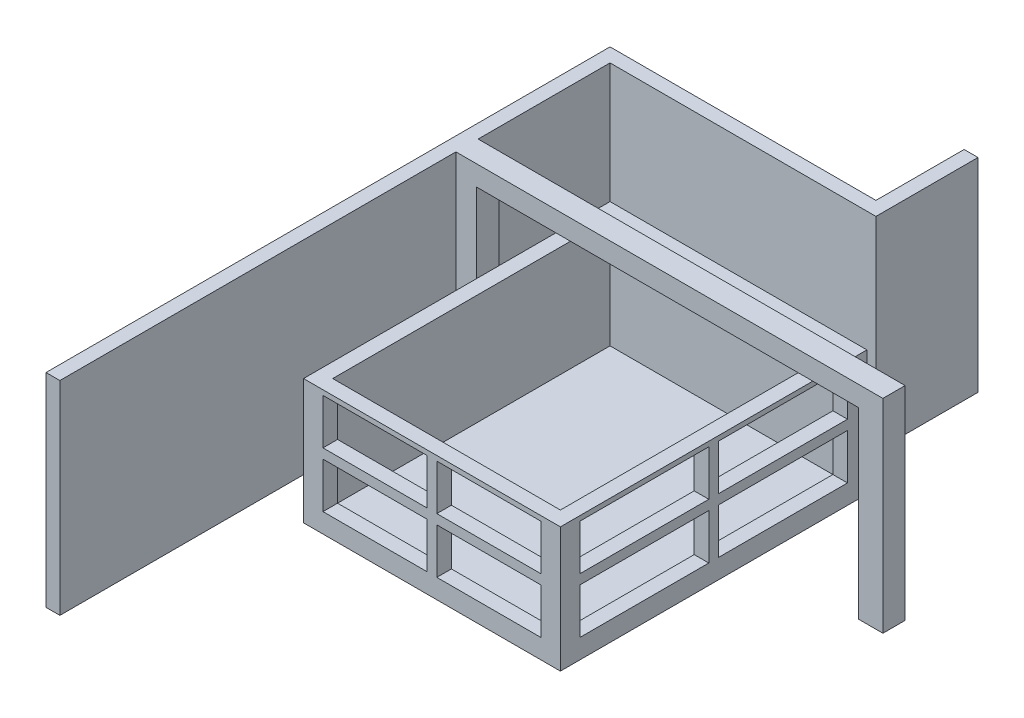
SolidWorks part; units mm, degrees
ref_plane "Front Plane" through (0, 0, 0) normal (0, 0, 1) x (1, 0, 0)
ref_plane "Top Plane" through (0, 0, 0) normal (0, 1, 0) x (1, 0, 0)
ref_plane "Right Plane" through (0, 0, 0) normal (1, 0, 0) x (0, 0, -1)
sketch "Sketch1" plane through (0, 0, 0) normal (0, 1, 0) x (1, 0, 0)
  line L0 (-1640, -1997.5) -> (-1640, 1997.5)
  line L1 (-1850, -2207.5) -> (1850, -2207.5)
  line L2 (-1850, -2207.5) -> (-1850, 2207.5)
  line L3 (-1850, 2207.5) -> (1850, 2207.5)
  line L4 (1850, -2207.5) -> (1850, 2207.5)
  line L5 (-1850, -2207.5) -> (1850, 2207.5) construction
  line L6 (-1850, 2207.5) -> (1850, -2207.5) construction
  line L7 (-1640, 1997.5) -> (1640, 1997.5)
  line L8 (1640, -1997.5) -> (1640, 1997.5)
  line L9 (-1640, -1997.5) -> (1640, -1997.5)
  point P0 (0, 0)
  dimension "D1" = 3700
  dimension "D2" = 4415
  dimension "D3" = 210
extrude "Boss-Extrude1" add sketch "Sketch1" along normal blind 210 contours L0 L9 L8 L7 | L1 L4 L3 L2 L9 L0 L7 L8 region at (0, 0, 0) region at (-1792.396, 0, 0)
extrude "Boss-Extrude2" add sketch "Sketch1<3>" along normal blind 1800
sketch "Sketch1<3>" plane through (0, 0, 0) normal (0, 1, 0) x (1, 0, 0) same geometry as "Sketch1"
sketch "Sketch2" plane through (0, 0, 2207.5) normal (0, 0, 1) x (1, 0, 0)
  line L1 (-1850, 1800) -> (-1640, 1800)
  line L2 (-1850, 1800) -> (-1850, 210)
  line L3 (-1850, 210) -> (-1640, 210)
  line L13 (-1640, 210) -> (0, 210)
  line L14 (1850, 1800) -> (1640, 1800)
  line L15 (1850, 1800) -> (1850, 210)
  line L16 (1850, 210) -> (1640, 210)
  line L18 (0, 210) -> (1640, 210)
  line L19 (0, 210) -> (0, 1005)
  line L20 (0, 1005) -> (0, 1800)
  line L21 (-1850, 1800) -> (1850, 1800) construction
  line L22 (0, 1800) -> (1640, 1800)
  line L23 (0, 1800) -> (-1640, 1800)
  line L24 (0, 1005) -> (-1640, 1005)
  line L25 (-1640, 1005) -> (-1640, 210)
  line L26 (-1640, 1005) -> (-1640, 1800)
  line L27 (1640, 1800) -> (1640, 1005)
  line L28 (1640, 1005) -> (0, 1005)
  line L29 (1640, 1005) -> (1640, 210)
  line L30 (0, 1800) -> (1640, 1800)
  line L31 (-70, 935) -> (-1570, 935)
  line L32 (-1570, 935) -> (-1570, 280)
  line L33 (-1570, 280) -> (-70, 280)
  line L34 (-70, 280) -> (-70, 935)
  line L35 (-70, 1730) -> (-1570, 1730)
  line L36 (-1570, 1075) -> (-1570, 1730)
  line L37 (-70, 1075) -> (-1570, 1075)
  line L38 (-70, 1075) -> (-70, 1730)
  line L39 (70, 1075) -> (70, 1730)
  line L40 (70, 1730) -> (1570, 1730)
  line L41 (1570, 1730) -> (1570, 1075)
  line L42 (1570, 1075) -> (70, 1075)
  line L43 (1570, 935) -> (70, 935)
  line L44 (70, 280) -> (70, 935)
  line L45 (70, 280) -> (1570, 280)
  line L46 (1570, 935) -> (1570, 280)
  line L47 (-1850, 0) -> (1850, 0) construction
  point P4 (1640, 150.3004)
  dimension "D1" = 210
  dimension "D6" = 210
  dimension "D2" = 70
  dimension "D3" = 70
  dimension "D4" = 70
  dimension "D5" = 70
extrude "Cut-Extrude1" cut sketch "Sketch2" against normal up to next contours L37 L38 L35 L36 | L33 L34 L31 L32 | L46 L43 L44 L45 | L42 L41 L40 L39 region at (-820, 607.5, 2207.5) region at (-820, 1402.5, 2207.5) region at (820, 1402.5, 2207.5) region at (820, 607.5, 2207.5)
extrude "Cut-Extrude2" cut sketch "Sketch2<3>" along normal blind 200 from surface contours L42 L41 L40 L39 | L37 L38 L35 L36 | L33 L34 L31 L32 | L46 L43 L44 L45 region at (-820, 607.5, 2207.5) region at (-820, 1402.5, 2207.5) region at (820, 1402.5, 2207.5) region at (820, 607.5, 2207.5) starting at face at (0, 900, -2207.5)
sketch "Sketch2<3>" plane through (0, 0, 2207.5) normal (0, 0, 1) x (1, 0, 0) same geometry as "Sketch2"
sketch "Sketch3" plane through (1850, 0, 0) normal (1, 0, 0) x (0, 0, -1)
  line L0 (-2207.5, 0) -> (2207.5, 0) construction
  line L1 (-2207.5, 1800) -> (-1997.5, 1800)
  line L2 (-2207.5, 1800) -> (-2207.5, 0)
  line L3 (-2207.5, 0) -> (-1997.5, 0)
  line L5 (-2207.5, 1800) -> (2207.5, 1800) construction
  line L6 (2207.5, 0) -> (1997.5, 0)
  line L7 (2207.5, 0) -> (2207.5, 1800)
  line L8 (2207.5, 1800) -> (1997.5, 1800)
  line L10 (-1997.5, 1800) -> (0, 1800)
  line L15 (0, 1800) -> (0, 1005)
  line L16 (0, 1005) -> (0, 210)
  line L17 (0, 1005) -> (1997.5, 1005)
  line L18 (0, 1005) -> (-1997.5, 1005)
  line L19 (-1997.5, 210) -> (-2207.5, 210)
  line L20 (-1997.5, 1800) -> (-1997.5, 1005)
  line L21 (-1997.5, 1005) -> (-1997.5, 210)
  line L22 (0, 1800) -> (1997.5, 1800)
  line L23 (1997.5, 1800) -> (1997.5, 1005)
  line L24 (1997.5, 1005) -> (1997.5, 210)
  line L25 (-1997.5, 210) -> (0, 210)
  line L26 (0, 210) -> (1997.5, 210)
  line L27 (1997.5, 210) -> (2207.5, 210)
  line L28 (-70, 935) -> (-1927.5, 935)
  line L29 (-1927.5, 935) -> (-1927.5, 280)
  line L30 (-1927.5, 280) -> (-70, 280)
  line L31 (-70, 935) -> (-70, 280)
  line L32 (-1927.5, 1730) -> (-1927.5, 1075)
  line L33 (-70, 1075) -> (-1927.5, 1075)
  line L34 (-70, 1730) -> (-70, 1075)
  line L35 (-1927.5, 1730) -> (-70, 1730)
  line L36 (70, 1730) -> (1927.5, 1730)
  line L37 (1927.5, 1730) -> (1927.5, 1075)
  line L38 (70, 1075) -> (1927.5, 1075)
  line L39 (70, 1730) -> (70, 1075)
  line L40 (70, 935) -> (70, 280)
  line L41 (70, 280) -> (1927.5, 280)
  line L42 (1927.5, 935) -> (1927.5, 280)
  line L43 (70, 935) -> (1927.5, 935)
  point P14 (1997.5, 223.504)
  dimension "D1" = 210
  dimension "D2" = 210
  dimension "D3" = 70
  dimension "D4" = 70
  dimension "D5" = 70
  dimension "D6" = 70
extrude "Cut-Extrude3" cut sketch "Sketch3" against normal up to next contours L35 L32 L33 L34 | L31 L28 L29 L30 | L43 L40 L41 L42 | L36 L39 L38 L37 region at (1850, 607.5, 998.75) region at (1850, 1402.5, 998.75) region at (1850, 1402.5, -998.75) region at (1850, 607.5, -998.75)
extrude "Cut-Extrude4" cut sketch "Sketch3<3>" along normal blind 200 from surface contours L43 L40 L41 L42 | L36 L39 L38 L37 | L35 L32 L33 L34 | L31 L28 L29 L30 region at (1850, 607.5, 998.75) region at (1850, 1402.5, 998.75) region at (1850, 1402.5, -998.75) region at (1850, 607.5, -998.75) starting at face at (-1850, 900, 0)
sketch "Sketch3<3>" plane through (1850, 0, 0) normal (1, 0, 0) x (0, 0, -1) same geometry as "Sketch3"
sketch "Sketch4" plane through (0, 0, 0) normal (0, 1, 0) x (1, 0, 0)
  line L0 (1380, 2807.5) -> (-2450, 2807.5)
  line L1 (-2450, 2807.5) -> (-2450, 907.5)
  line L2 (-2450, 907.5) -> (-2150, 907.5)
  line L3 (-2150, 907.5) -> (-2150, 587.5)
  line L4 (-2150, 587.5) -> (-2450, 587.5)
  line L5 (-2450, 587.5) -> (-2450, -5116.7685)
  line L6 (1850, 2207.5) -> (-1850, 2207.5) construction
  line L7 (-1850, 2207.5) -> (-1850, -2207.5) construction
  line L8 (1380, 2807.5) -> (1380, 4277.4756)
  line L9 (1850, -2207.5) -> (1850, 2207.5) construction
  line L10 (-2450, 907.5) -> (-2450, 587.5)
  line L11 (-2150, 907.5) -> (3350, 907.5) construction
  line L12 (-2450, -5116.7685) -> (-2650, -5116.7685)
  line L13 (3350, 907.5) -> (3700, 907.5)
  line L14 (3350, 907.5) -> (3350, 587.5)
  line L15 (3350, 587.5) -> (3700, 587.5)
  line L16 (3700, 907.5) -> (3700, 587.5)
  line L17 (-2650, -5116.7685) -> (-2650, 3007.5)
  line L18 (1380, 4277.4756) -> (1180, 4277.4756)
  line L19 (1180, 4277.4756) -> (1180, 3007.5)
  line L20 (1180, 3007.5) -> (-2650, 3007.5)
  line L21 (1180, 3007.5) -> (1180, 2807.5) construction
  line L22 (1180, 3007.5) -> (1380, 3007.5) construction
  line L23 (-2450, 2807.5) -> (-2650, 2807.5) construction
  dimension "D1" = 600
  dimension "D2" = 600
  dimension "D3" = 320
  dimension "D4" = 300
  dimension "D5" = 1900
  dimension "D6" = 470
  dimension "D7" = 1500
  dimension "D8" = 350
  dimension "D9" = 200
extrude "Boss-Extrude3" add sketch "Sketch4" along normal blind 2640 separate body contours L16 L13 L14 L15 | L2 L10 L4 L3 region at (-2300, 0, -747.5) region at (3525, 0, -747.5)
sketch "Sketch5" plane through (0, 2640, 0) normal (0, 1, 0) x (1, 0, 0)
  line L1 (-2450, 907.5) -> (3700, 907.5)
  line L2 (-2450, 907.5) -> (-2450, 587.5)
  line L3 (-2450, 587.5) -> (3700, 587.5)
  line L4 (3700, 907.5) -> (3700, 587.5)
extrude "Boss-Extrude4" add sketch "Sketch5" along normal offset from surface (290 mm away) 2930 up to face at (-2300, 0, -747.5)
extrude "Boss-Extrude5" add sketch "Sketch4<3>" along normal up to surface (2930 mm away) contours L19 L20 L17 L12 L5 L10 L1 L0 L8 L18 region at (-535, 0, -2909.7217) up to face at (625, 2930, -747.5)
sketch "Sketch4<3>" plane through (0, 0, 0) normal (0, 1, 0) x (1, 0, 0) same geometry as "Sketch4"
